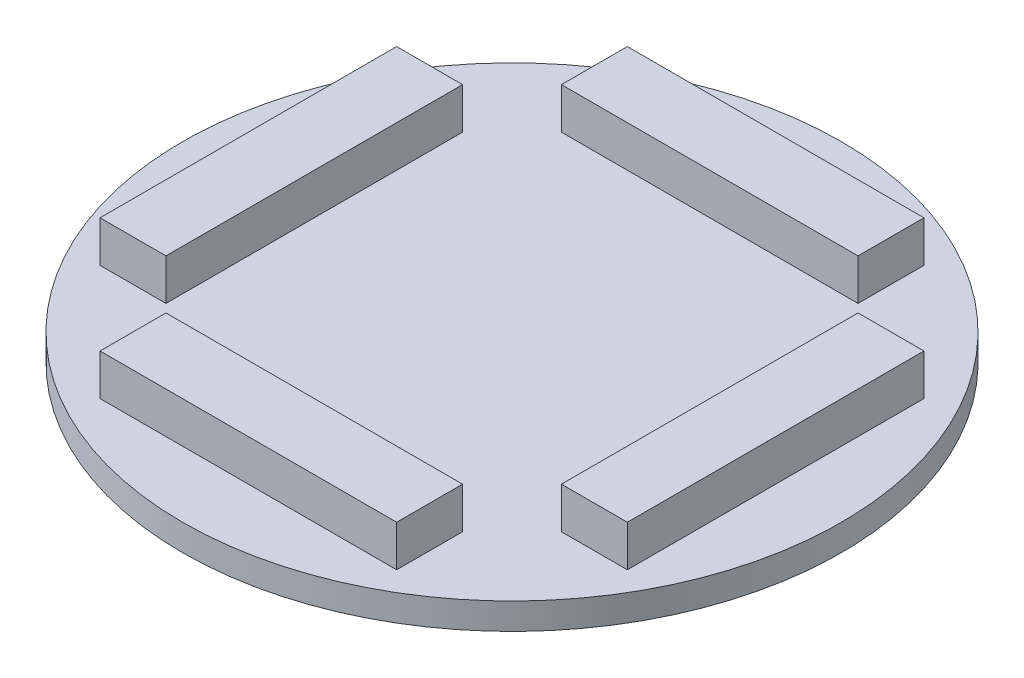
SolidWorks part; units mm, degrees
material "A-Glass Fiber"
ref_plane "Front Plane" through (0, 0, 0) normal (0, 0, 1) x (1, 0, 0)
ref_plane "Top Plane" through (0, 0, 0) normal (0, 1, 0) x (1, 0, 0)
ref_plane "Right Plane" through (0, 0, 0) normal (1, 0, 0) x (0, 0, -1)
sketch "Sketch1" plane through (0, 0, 0) normal (0, 1, 0) x (1, 0, 0)
  circle A0 centre (0, 0) radius 20
  dimension "D1" = 40
extrude "PCB" add sketch "Sketch1" along normal blind 1.6 contours A0
sketch "Sketch2" plane through (0, 1.6, 0) normal (0, 1, 0) x (1, 0, 0)
  line L0 (0, 20) -> (0, 0) construction
  line L1 (-9, 16) -> (9, 16)
  line L2 (-9, 16) -> (-9, 12)
  line L3 (-9, 12) -> (9, 12)
  line L4 (9, 16) -> (9, 12)
  circle A0 centre (0, 0) radius 20 construction
  point P9 (0, 16)
  dimension "D1" = 4
  dimension "D2" = 18
  dimension "D3" = 16
extrude "Hirose Connector Stack" add sketch "Sketch2" along normal blind 2.5 contours L1 L4 L3 L2
pattern_circular "CirPattern1" count 4 over 360 about axis through (0, 1.6, 0) along (0, 1, 0) of "Hirose Connector Stack"
